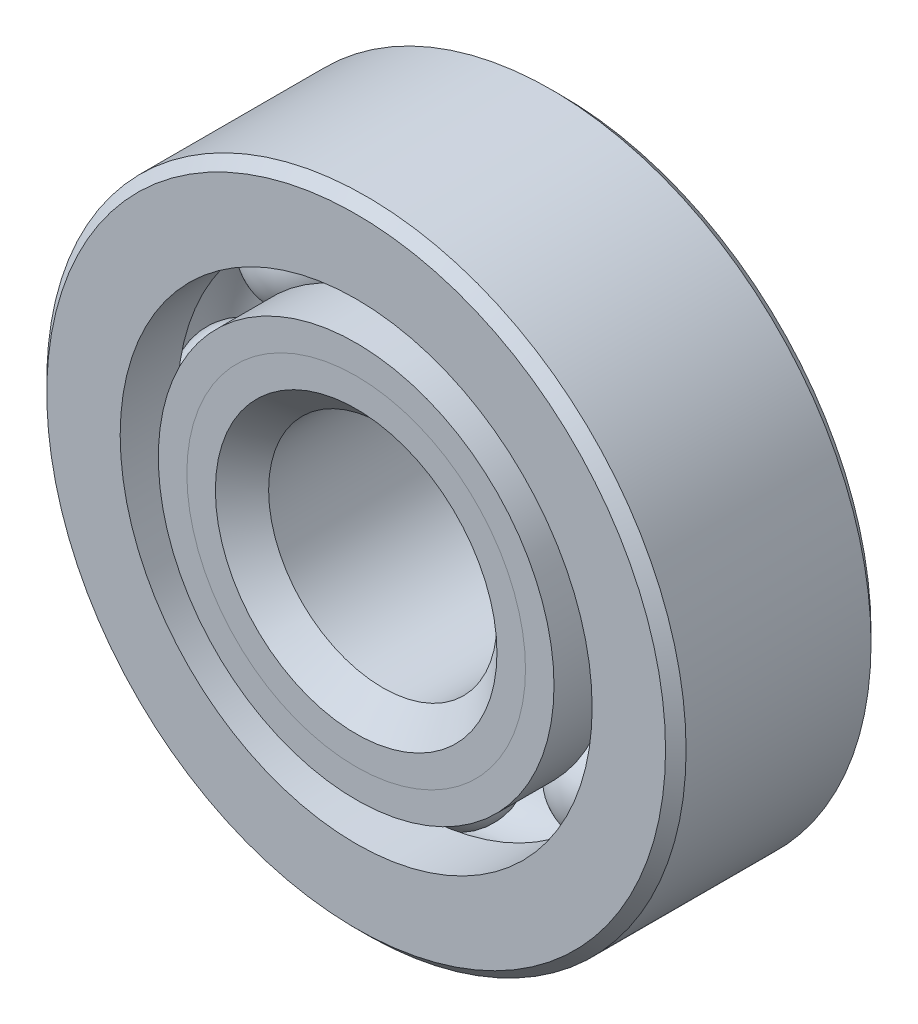
SolidWorks part; units mm, degrees
ref_plane "Front Plane" through (0, 0, 0) normal (0, 0, 1) x (1, 0, 0)
ref_plane "Top Plane" through (0, 0, 0) normal (0, 1, 0) x (1, 0, 0)
ref_plane "Right Plane" through (0, 0, 0) normal (1, 0, 0) x (0, 0, -1)
sketch "Sketch1" plane through (0, 0, 0) normal (1, 0, 0) x (0, 0, -1)
  line L0 (-3.5719, 0) -> (3.5719, 0) construction
  line L1 (0, 11.1125) -> (0, -11.1125) construction
  line L2 (3.2147, 11.1125) -> (-3.2147, 11.1125)
  line L3 (-3.2147, 11.1125) -> (-3.5719, 10.7553)
  line L4 (-3.5719, 10.7553) -> (-3.5719, 8.2035)
  line L5 (-3.5719, 8.2035) -> (-1.5875, 8.2035)
  line L6 (3.5719, 8.2035) -> (1.5875, 8.2035)
  line L7 (3.5719, 10.7553) -> (3.5719, 8.2035)
  line L8 (3.2147, 11.1125) -> (3.5719, 10.7553)
  line L9 (0, 11.1125) -> (0, 7.5406) construction
  line L10 (0, 7.5406) -> (0, 3.9688) construction
  arc A0 (-1.5875, 8.2035) -> (1.5875, 8.2035) centre (0, 7.5406) cw
  point P14 (0, 3.9688)
  dimension "Width" = 7.1437
  dimension "OD" = 22.225
  dimension "D1" = 45
  dimension "D2" = 0.3572
  dimension "D3" = 3.175
  dimension "D4" = 0.6629
revolve "Revolve1" add sketch "Sketch1" angle 360 about L0
sketch "Sketch2" plane through (0, 0, 0) normal (1, 0, 0) x (0, 0, -1)
  line L0 (-3.5719, 6.8777) -> (-1.5875, 6.8777)
  line L1 (-3.5719, 10.7553) -> (-3.5719, -10.7553) construction
  line L2 (-3.5719, 6.8777) -> (-3.5719, 5.8861)
  line L3 (-3.5719, 5.8861) -> (-2.5803, 4.8945)
  line L4 (-2.5803, 4.8945) -> (0, 4.8945)
  line L5 (0, 11.1125) -> (0, -11.1125) construction
  line L6 (0, 4.8945) -> (0, 5.8203)
  line L7 (0, 5.8203) -> (0, 3.9688) construction
  line L8 (-3.5719, 6.8777) -> (-3.5719, 4.8945) construction
  line L9 (-3.5719, 4.8945) -> (-2.5803, 4.8945) construction
  arc A0 (-1.5875, 6.8777) -> (0, 5.8203) centre (0, 7.5406) ccw
  arc A1 (1.5875, 8.2035) -> (-1.5875, 8.2035) centre (0, 7.5406) ccw construction
  circle A2 centre (0, 7.5406) radius 1.7204 construction
  dimension "D1" = 45
revolve "Revolve2" add sketch "Sketch2" angle 360 about L0
sketch "Sketch3" plane through (0, 0, 0) normal (1, 0, 0) x (0, 0, -1)
  line L0 (-3.5719, 5.8861) -> (-2.5803, 4.8945)
  line L1 (-2.5803, 4.8945) -> (0, 4.8945)
  line L2 (0, 4.8945) -> (0, 5.8203)
  line L3 (-3.5719, 5.8861) -> (-3.5719, 4.8945)
  line L4 (-3.5719, 6.8777) -> (-3.5719, 4.8945) construction
  line L5 (-3.5719, 4.8945) -> (-2.6461, 3.9688)
  line L6 (-2.6461, 3.9688) -> (3.2147, 3.9688)
  line L7 (3.2147, 11.1125) -> (3.2147, -11.1125) construction
  line L8 (3.2147, 3.9688) -> (3.5719, 4.3259)
  line L9 (3.5719, -10.7553) -> (3.5719, 10.7553) construction
  line L10 (3.5719, 4.3259) -> (3.5719, 6.8777)
  line L11 (3.5719, 6.8777) -> (1.5875, 6.8777)
  line L13 (3.2147, 11.1125) -> (3.5719, 10.7553) construction
  circle A0 centre (0, 7.5406) radius 1.7204 construction
  arc A1 (1.5875, 6.8777) -> (0, 5.8203) centre (0, 7.5406) cw
revolve "Revolve3" add sketch "Sketch3" angle 360 about L0
sketch "Sketch4" plane through (0, 0, 0) normal (1, 0, 0) x (0, 0, -1)
  line L0 (-1.7204, 7.5406) -> (1.7204, 7.5406)
  circle A1 centre (0, 7.5406) radius 1.7204 construction
  arc A2 (-1.7204, 7.5406) -> (1.7204, 7.5406) centre (0, 7.5406) cw
  arc A3 (1.5875, 8.2035) -> (-1.5875, 8.2035) centre (0, 7.5406) ccw construction
revolve "Revolve4" add sketch "Sketch4" angle 360 about L0
ref_axis "Axis1" through (0, 0, -3.5719) along (0, 0, 1)
pattern_circular "CirPattern1" count 8 every 45 about axis through (0, 0, -3.5719) along (0, 0, 1) of bodies 104
equation "\"D2@Sketch1\" = \"Width@Sketch1\"*.05"
equation "\"D3@Sketch1\" = \"Width@Sketch1\"/2.25"
equation "\"D4@Sketch1\" = (((\"OD@Sketch1\"-\"Width@Sketch1\")/2)/3.25)/3.5"
equation "\"D2@CirPattern1\" = 360/\"Balls@CirPattern1\""
